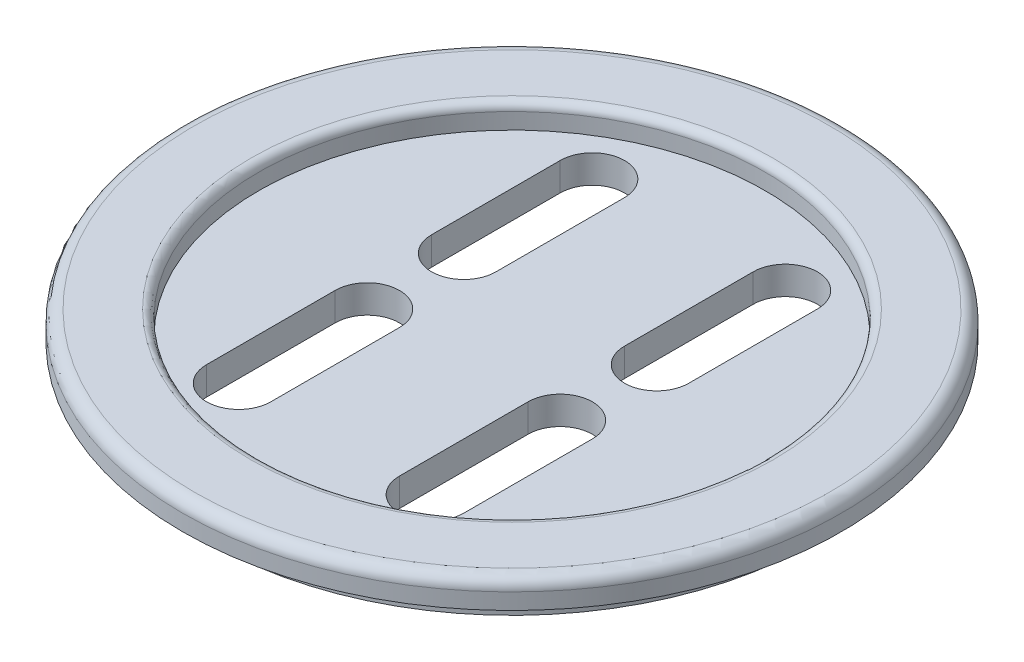
SolidWorks part; units mm, degrees
ref_plane "Front Plane" through (0, 0, 0) normal (0, 0, 1) x (1, 0, 0)
ref_plane "Top Plane" through (0, 0, 0) normal (0, 1, 0) x (1, 0, 0)
ref_plane "Right Plane" through (0, 0, 0) normal (1, 0, 0) x (0, 0, -1)
sketch "Sketch1" plane through (0, 0, 0) normal (0, 1, 0) x (1, 0, 0)
  line L0 (-120, 220) -> (-120, 60) construction
  line L3 (-80, 220) -> (-80, 60)
  line L6 (-160, 220) -> (-160, 60)
  line L7 (0, 0) -> (675.4331, 0) construction
  line L10 (0, 0) -> (0, 601.1586) construction
  line L11 (-120, -220) -> (-120, -60) construction
  line L12 (-80, -220) -> (-80, -60)
  line L13 (-160, -220) -> (-160, -60)
  line L14 (120, 220) -> (120, 60) construction
  line L15 (80, 220) -> (80, 60)
  line L16 (160, 220) -> (160, 60)
  line L17 (120, -220) -> (120, -60) construction
  line L18 (80, -220) -> (80, -60)
  line L19 (160, -220) -> (160, -60)
  circle A0 centre (0, 0) radius 375
  circle A2 centre (0, 0) radius 410
  circle A3 centre (0, 0) radius 315
  arc A8 (-80, 220) -> (-160, 220) centre (-120, 220) ccw
  arc A9 (-160, 60) -> (-80, 60) centre (-120, 60) ccw
  arc A12 (-80, -220) -> (-160, -220) centre (-120, -220) cw
  arc A13 (-160, -60) -> (-80, -60) centre (-120, -60) cw
  arc A14 (80, 220) -> (160, 220) centre (120, 220) cw
  arc A15 (160, 60) -> (80, 60) centre (120, 60) cw
  arc A16 (80, -220) -> (160, -220) centre (120, -220) ccw
  arc A17 (160, -60) -> (80, -60) centre (120, -60) ccw
  point P7 (-120, 140)
  point P16 (-120, -140)
  point P21 (0, 0)
  point P24 (120, 140)
  point P31 (120, -140)
  point P36 (0, 0)
  dimension "D1" = 630
  dimension "D2" = 750
  dimension "D3" = 820
  dimension "D7" = 40
  dimension "D4" = 60
  dimension "D5" = 160
  dimension "D6" = 120
extrude "Boss-Extrude1" add sketch "Sketch1" against normal blind 30 contours A0
extrude "Boss-Extrude2" add sketch "Sketch1<7>" along normal blind 35 contours A2
sketch "Sketch1<7>" plane through (0, 0, 0) normal (0, 1, 0) x (1, 0, 0) same geometry as "Sketch1"
extrude "Cut-Extrude1" cut sketch "Sketch1<10>" against normal through all both and the other way through all contours A17 L18 A16 L19 | A13 L12 A12 L13 | A8 L6 A9 L3 | L15 A15 L16 A14
sketch "Sketch1<10>" plane through (0, 0, 0) normal (0, 1, 0) x (1, 0, 0) same geometry as "Sketch1"
extrude "Cut-Extrude2" cut sketch "Sketch1<14>" against normal blind 30 from surface contours A3 starting at face at (120, 35, 140)
sketch "Sketch1<14>" plane through (0, 0, 0) normal (0, 1, 0) x (1, 0, 0) same geometry as "Sketch1"
fillet "Fillet1" radius 15 1 edges at (0, 35, 410)
fillet "Fillet2" radius 10 1 edges at (0, 35, 315)
